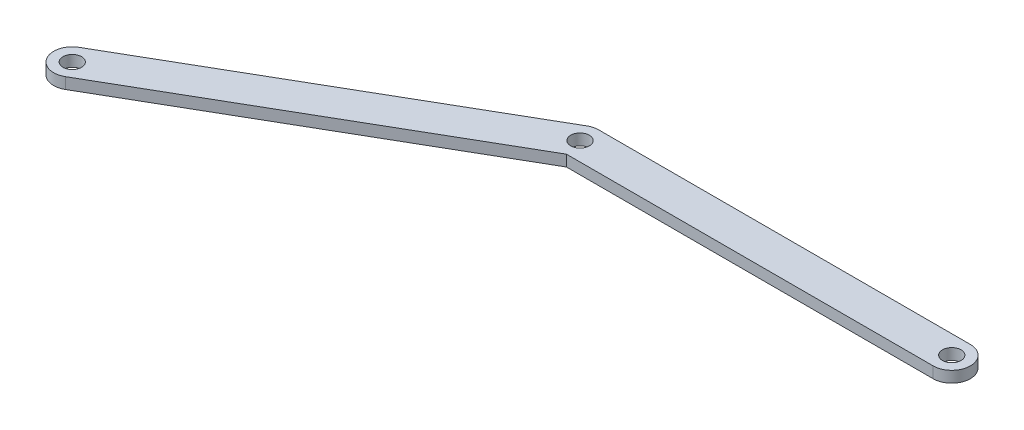
SolidWorks part; units mm, degrees
ref_plane "Front Plane" through (0, 0, 0) normal (0, 0, 1) x (1, 0, 0)
ref_plane "Top Plane" through (0, 0, 0) normal (0, 1, 0) x (1, 0, 0)
ref_plane "Right Plane" through (0, 0, 0) normal (1, 0, 0) x (0, 0, -1)
sketch "Sketch1" plane through (0, 0, 0) normal (0, 1, 0) x (1, 0, 0)
  line L0 (-63.5, 0) -> (63.5, 0) construction
  line L1 (-63.5, 6.35) -> (63.5, 6.35)
  line L2 (-63.5, -6.35) -> (63.5, -6.35)
  arc A0 (-63.5, 6.35) -> (-63.5, -6.35) centre (-63.5, 0) ccw
  arc A1 (63.5, -6.35) -> (63.5, 6.35) centre (63.5, 0) ccw
  circle A2 centre (-63.5, 0) radius 3.175
  circle A3 centre (63.5, 0) radius 3.175
  point P3 (0, 0)
  dimension "D2" = 6.35
  dimension "D3" = 6.35
  dimension "D4" = 6.35
  dimension "D1" = 127
extrude "Boss-Extrude1" add sketch "Sketch1" along normal blind 3.81
sketch "Sketch2" plane through (0, 0, 0) normal (0, 1, 0) x (1, 0, 0)
  line L0 (-173.4852, -63.5) -> (-63.5, 0) construction
  line L1 (-176.6602, -58.0007) -> (-66.675, 5.4993)
  line L2 (-170.3102, -68.9993) -> (-60.325, -5.4993)
  line L3 (-63.5, 0) -> (63.5, 0) construction
  arc A0 (-176.6602, -58.0007) -> (-170.3102, -68.9993) centre (-173.4852, -63.5) ccw
  arc A1 (-60.325, -5.4993) -> (-66.675, 5.4993) centre (-63.5, 0) ccw
  circle A2 centre (-173.4852, -63.5) radius 3.175
  point P2 (-118.4926, -31.75)
  dimension "D3" = 6.35
  dimension "D4" = 6.35
  dimension "D1" = 150
  dimension "D2" = 127
extrude "Boss-Extrude2" add sketch "Sketch2" along normal blind 3.81
extrude "Cut-Extrude4" cut sketch "Sketch1<2>" against normal blind 3.81 and the other way blind 3.81 contours A2
sketch "Sketch1<2>" plane through (0, 0, 0) normal (0, 1, 0) x (1, 0, 0) same geometry as "Sketch1"
